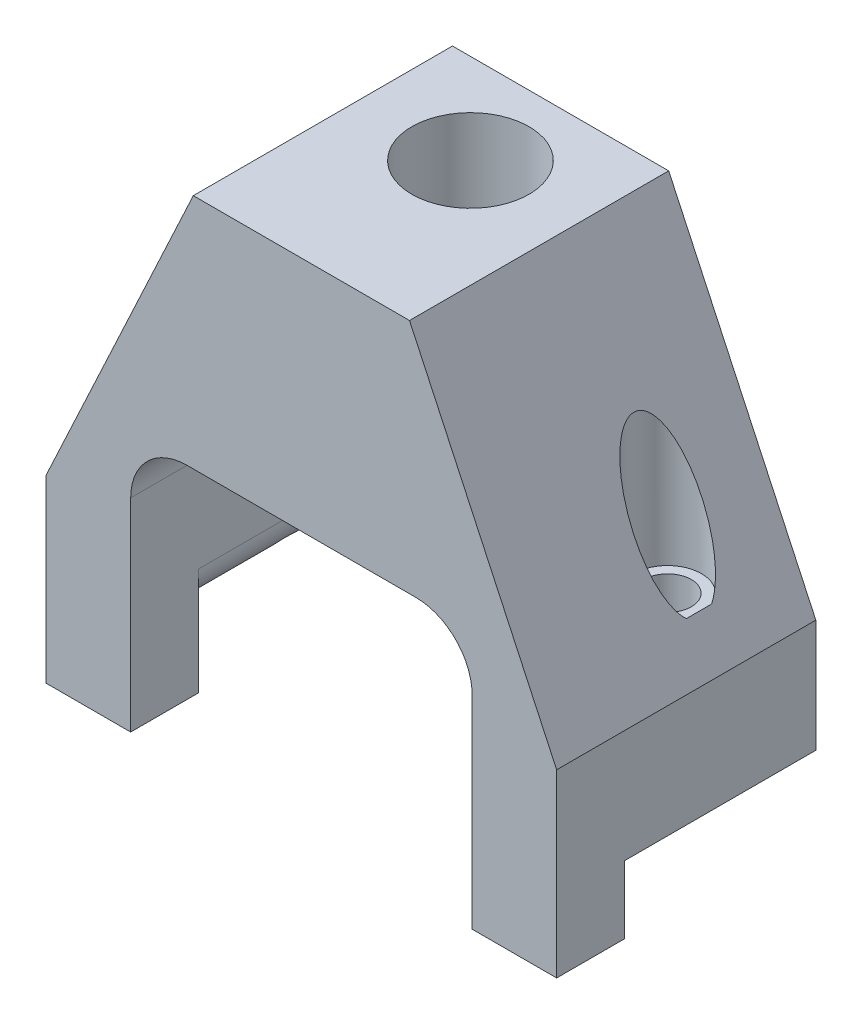
SolidWorks part; units mm, degrees
ref_plane "Front Plane" through (0, 0, 0) normal (0, 0, 1) x (1, 0, 0)
ref_plane "Top Plane" through (0, 0, 0) normal (0, 1, 0) x (1, 0, 0)
ref_plane "Right Plane" through (0, 0, 0) normal (1, 0, 0) x (0, 0, -1)
sketch "Sketch1" plane through (0, 0, 0) normal (0, 0, 1) x (1, 0, 0)
  line L0 (16.91, 0) -> (18.9, 0)
  line L2 (0, 1.76) -> (0, 6)
  line L3 (2.5, 8.5) -> (12.65, 8.5)
  line L4 (15.15, 1.76) -> (15.15, 6)
  line L5 (-3.75, 0) -> (-1.76, 0)
  line L6 (-3.75, 0) -> (-3.75, 19)
  line L7 (-3.75, 19) -> (18.9, 19)
  line L8 (18.9, 0) -> (18.9, 19)
  arc A0 (12.65, 8.5) -> (15.15, 6) centre (12.65, 6) cw
  arc A1 (0, 6) -> (2.5, 8.5) centre (2.5, 6) cw
  arc A2 (16.91, 0) -> (15.15, 1.76) centre (16.91, 1.76) cw
  arc A3 (-1.76, 0) -> (0, 1.76) centre (-1.76, 1.76) ccw
  point P9 (0, 8.5)
  point P16 (15.15, 0)
  point P19 (0, 0)
  dimension "D2" = 2.5
  dimension "D7" = 1.76
  dimension "D1" = 8.5
  dimension "D3" = 15.15
  dimension "D4" = 3.75
  dimension "D5" = 3.75
  dimension "D6" = 19
extrude "Boss-Extrude1" add sketch "Sketch1" against normal blind 11.5 contours L7 L8 L0 A2 L4 A0 L3 A1 L2 A3 L5 L6
sketch "Sketch3" plane through (0, 19, 0) normal (0, 1, 0) x (1, 0, 0)
  line L0 (-3.75, 11.5) -> (18.9, 11.5) construction
  line L1 (7.575, 11.5) -> (7.575, 0) construction
  line L2 (-3.75, 0) -> (18.9, 0) construction
  circle A0 centre (-1.425, 7.25) radius 1.05
  circle A1 centre (16.575, 7.25) radius 1.05
  dimension "D2" = 9
  dimension "D3" = 2.1
  dimension "D1" = 4.25
extrude "Cut-Extrude1" cut sketch "Sketch3" against normal through all both and the other way through all
sketch "Sketch4" plane through (0, 0, 0) normal (0, -1, 0) x (1, 0, 0)
  line L0 (15.15, -11.5) -> (15.15, 0) construction
  line L1 (-3.75, 0) -> (0, 0)
  line L2 (-3.75, 0) -> (-3.75, -3)
  line L3 (-3.75, -3) -> (0, -3)
  line L4 (0, 0) -> (0, -3)
  line L5 (18.9, 0) -> (15.15, 0)
  line L6 (18.9, 0) -> (18.9, -3)
  line L7 (18.9, -3) -> (15.15, -3)
  line L8 (15.15, 0) -> (15.15, -3)
  line L9 (0, -11.5) -> (0, 0) construction
  dimension "D1" = 3
  dimension "D2" = 3
extrude "Boss-Extrude2" add sketch "Sketch4" along normal blind 3 and the other way blind 11.5 contours L5 L8 L7 L6 | L3 L4 L1 L2 region at (17.025, 0, -1.5)
sketch "Sketch5" plane through (0, 19, 0) normal (0, 1, 0) x (1, 0, 0)
  line L0 (7.575, 11.5) -> (7.575, 0) construction
  line L1 (-3.75, 11.5) -> (18.9, 11.5) construction
  line L2 (-3.75, 0) -> (18.9, 0) construction
  circle A0 centre (7.575, 7.5) radius 1.25
  dimension "D1" = 2.5
  dimension "D2" = 4
extrude "Cut-Extrude2" cut sketch "Sketch5" against normal through all both and the other way through all contours A0
chamfer "Chamfer1" distance 14 angle 25 1 edges at (-3.75, 19, -5.75) first distance on face at (-3.75, 5.3333, -4.8333)
chamfer "Chamfer2" distance 14 angle 25 1 edges at (18.9, 19, -5.75) first distance on face at (18.9, 5.3333, -4.8333)
sketch "Sketch6" plane through (0, 19, 0) normal (0, 1, 0) x (1, 0, 0)
  circle A0 centre (7.575, 7.5) radius 2.6
  dimension "D1" = 5.2
extrude "Cut-Extrude3" cut sketch "Sketch6" against normal blind 5
sketch "Sketch7" plane through (0, 19, 0) normal (0, 1, 0) x (1, 0, 0)
  circle A0 centre (-1.425, 7.25) radius 1.5
  circle A1 centre (16.575, 7.25) radius 1.5
  dimension "D1" = 3
  dimension "D2" = 3
extrude "Cut-Extrude4" cut sketch "Sketch7" against normal blind 12
